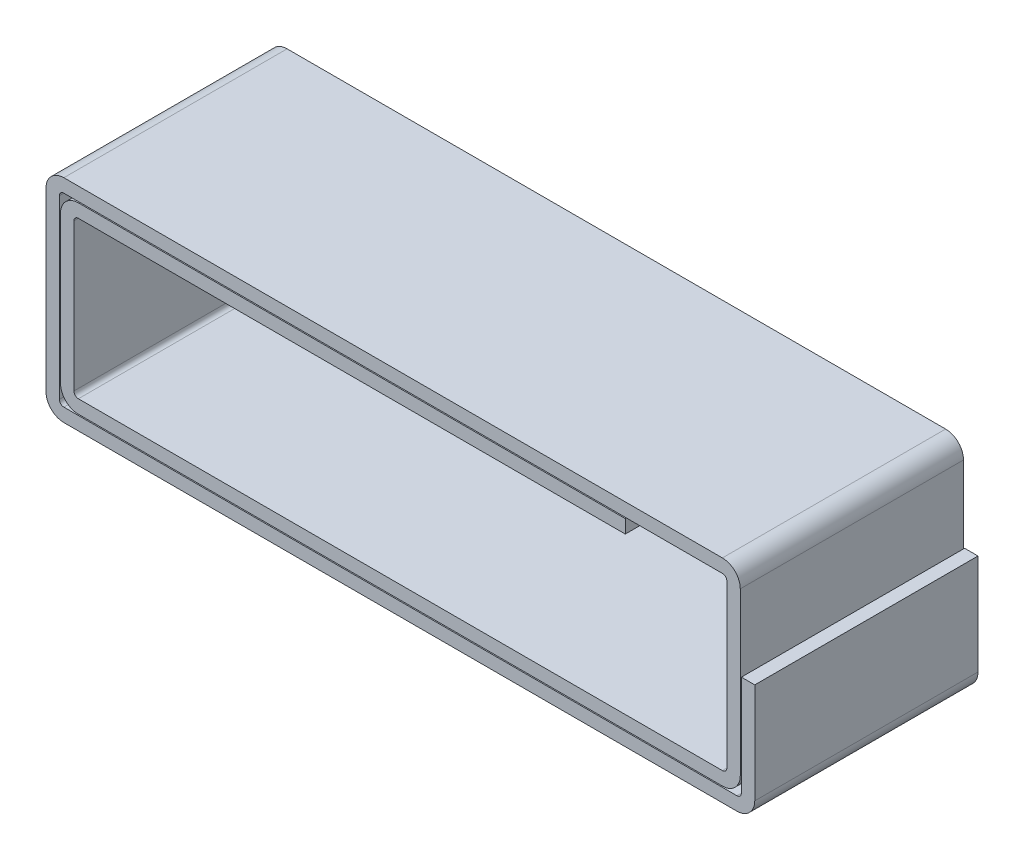
SolidWorks part; units mm, degrees
material "Velcro, Nylon"
ref_plane "Front Plane" through (0, 0, 0) normal (0, 0, 1) x (1, 0, 0)
ref_plane "Top Plane" through (0, 0, 0) normal (0, 1, 0) x (1, 0, 0)
ref_plane "Right Plane" through (0, 0, 0) normal (1, 0, 0) x (0, 0, -1)
sketch "Sketch1" plane through (0, 0, 0) normal (0, 0, 1) x (1, 0, 0)
  line L0 (-29.85, 14.2) -> (-29.85, 1) construction
  line L5 (-28.85, 0) -> (28.85, 0) construction
  line L6 (29.85, 1) -> (29.85, 15.5) construction
  line L7 (-28.85, 15.2) -> (20.15, 15.2) construction
  line L8 (28.85, 16.5) -> (-30.15, 16.5) construction
  line L9 (-31.15, 15.5) -> (-31.15, -0.3) construction
  line L10 (-30.15, -1.3) -> (30.15, -1.3) construction
  line L11 (31.15, -0.3) -> (31.15, 8.7) construction
  line L12 (-28.85, 15.8) -> (20.15, 15.8)
  line L13 (-30.45, 14.2) -> (-30.45, 1)
  line L14 (-28.85, -0.6) -> (28.85, -0.6)
  line L15 (30.45, 1) -> (30.45, 15.5)
  line L16 (28.85, 17.1) -> (-30.15, 17.1)
  line L17 (-31.75, 15.5) -> (-31.75, -0.3)
  line L18 (-30.15, -1.9) -> (30.15, -1.9)
  line L19 (31.75, -0.3) -> (31.75, 8.7)
  line L20 (-28.85, 14.6) -> (20.15, 14.6)
  line L21 (-29.25, 14.2) -> (-29.25, 1)
  line L22 (-28.85, 0.6) -> (28.85, 0.6)
  line L23 (29.25, 1) -> (29.25, 15.5)
  line L24 (28.85, 15.9) -> (-30.15, 15.9)
  line L25 (-30.55, 15.5) -> (-30.55, -0.3)
  line L26 (-30.15, -0.7) -> (30.15, -0.7)
  line L27 (30.55, -0.3) -> (30.55, 8.7)
  line L28 (20.15, 15.8) -> (20.15, 14.6)
  line L29 (30.55, 8.7) -> (31.75, 8.7)
  arc A0 (29.85, 15.5) -> (28.85, 16.5) centre (28.85, 15.5) ccw construction
  arc A1 (28.85, 0) -> (29.85, 1) centre (28.85, 1) ccw construction
  arc A2 (-29.85, 1) -> (-28.85, 0) centre (-28.85, 1) ccw construction
  arc A3 (-31.15, -0.3) -> (-30.15, -1.3) centre (-30.15, -0.3) ccw construction
  arc A4 (-30.15, 16.5) -> (-31.15, 15.5) centre (-30.15, 15.5) ccw construction
  arc A5 (-29.85, 14.2) -> (-28.85, 15.2) centre (-28.85, 14.2) cw construction
  arc A6 (30.15, -1.3) -> (31.15, -0.3) centre (30.15, -0.3) ccw construction
  arc A7 (-30.45, 14.2) -> (-28.85, 15.8) centre (-28.85, 14.2) cw
  arc A8 (-30.45, 1) -> (-28.85, -0.6) centre (-28.85, 1) ccw
  arc A9 (28.85, -0.6) -> (30.45, 1) centre (28.85, 1) ccw
  arc A10 (30.45, 15.5) -> (28.85, 17.1) centre (28.85, 15.5) ccw
  arc A11 (-30.15, 17.1) -> (-31.75, 15.5) centre (-30.15, 15.5) ccw
  arc A12 (-31.75, -0.3) -> (-30.15, -1.9) centre (-30.15, -0.3) ccw
  arc A13 (30.15, -1.9) -> (31.75, -0.3) centre (30.15, -0.3) ccw
  arc A14 (-29.25, 14.2) -> (-28.85, 14.6) centre (-28.85, 14.2) cw
  arc A15 (-29.25, 1) -> (-28.85, 0.6) centre (-28.85, 1) ccw
  arc A16 (28.85, 0.6) -> (29.25, 1) centre (28.85, 1) ccw
  arc A17 (29.25, 15.5) -> (28.85, 15.9) centre (28.85, 15.5) ccw
  arc A18 (-30.15, 15.9) -> (-30.55, 15.5) centre (-30.15, 15.5) ccw
  arc A19 (-30.55, -0.3) -> (-30.15, -0.7) centre (-30.15, -0.3) ccw
  arc A20 (30.15, -0.7) -> (30.55, -0.3) centre (30.15, -0.3) ccw
  point P21 (0, 0)
  dimension "D3" = 1
  dimension "D9" = 1
  dimension "D1" = 1.3
  dimension "D2" = 1.3
  dimension "D4" = 59
  dimension "D5" = 14.5
  dimension "D6" = 49
  dimension "D7" = 14
  dimension "D8" = 1.3
  dimension "D10" = 9
  dimension "D11" = 0.6
  dimension "D12" = 0.6
extrude "Boss-Extrude2" add sketch "Sketch1" along normal mid plane 20 contours L16 A11 L17 A12 L18 A13 L19 L29 L27 A20 L26 A19 L25 A18 L24 A17 L23 A16 L22 A15 L21 A14 L20 L28 L12 A7 L13 A8 L14 A9 L15 A10
